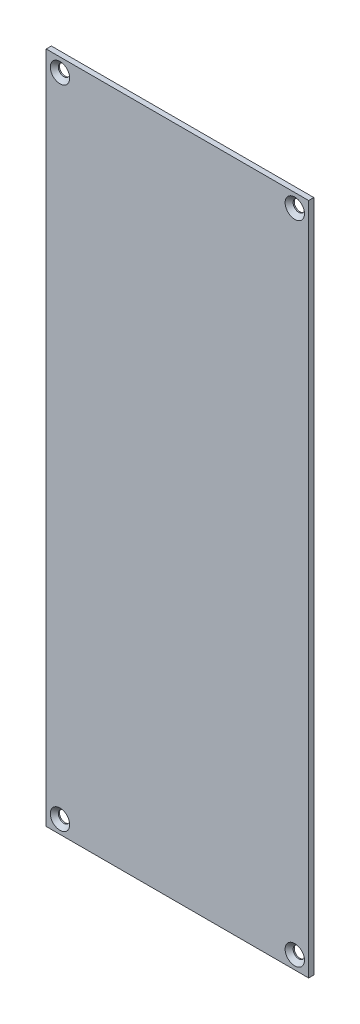
SolidWorks part; units mm, degrees
ref_plane "Front Plane" through (0, 0, 0) normal (0, 0, 1) x (1, 0, 0)
ref_plane "Top Plane" through (0, 0, 0) normal (0, 1, 0) x (1, 0, 0)
ref_plane "Right Plane" through (0, 0, 0) normal (1, 0, 0) x (0, 0, -1)
sketch "Sketch1" plane through (0, 0, 0) normal (0, 0, 1) x (1, 0, 0)
  line L0 (0, 130.33) -> (0, 0)
  line L1 (50.8, 130.33) -> (0, 130.33)
  line L2 (50.8, 0) -> (50.8, 130.33)
  line L3 (0, 0) -> (50.8, 0)
  point P0 (0, 0)
  point P2 (0, 0)
  point P3 (0, 0)
  point P4 (0, 0)
  point P5 (0, 0)
  dimension "D1" = 50.8
  dimension "D2" = 130.33
extrude "Boss-Extrude1" add sketch "Sketch1" along normal blind 1
hole_wizard "CSK for M2 Flat Head Machine Screw1" positions "Sketch6" profile "Sketch4" countersink size "M2" standard "ANSI Metric" end condition up to next
sketch "Sketch6" plane through (0, 0, 1) normal (0, 0, 1) x (1, 0, 0)
  line L2 (2.6725, 127.7025) -> (48.1225, 127.7025) construction
  line L3 (48.1225, 127.7025) -> (48.1225, 2.5625) construction
  line L4 (48.1225, 2.5625) -> (2.6725, 2.5625) construction
  line L5 (2.6725, 2.5625) -> (2.6725, 127.7025) construction
  line L16 (50.8, 130.33) -> (0, 130.33) construction
  line L17 (0, 130.33) -> (0, 0) construction
  point P3 (48.1225, 127.7025)
  point P6 (2.6725, 2.5625)
  point P9 (48.1225, 2.5625)
  point P15 (2.6725, 127.7025)
  point P74 (0.6945, 0.6945)
  point P75 (42.7862, 126.8117)
  point P76 (0, 0)
  dimension "D1" = 2.6275
  dimension "D2" = 2.6725
  dimension "D3" = 45.45
  dimension "D4" = 125.14
sketch "Sketch4" plane through (48.1225, 127.7025, 1) normal (1, 0, 0) x (0, -1, 0)
  line L0 (0, 0) -> (0, 1)
  line L1 (0, 1) -> (1.1, 1)
  line L2 (1.1, 1) -> (1.1, 0.775)
  line L3 (1.1, 0.775) -> (1.875, 0)
  line L5 (1.875, 0) -> (0, 0)
  line L6 (-1.1, 0.775) -> (-1.875, 0) construction
  line L11 (0, -6.35) -> (0, 107.95) construction
  dimension "Thru Hole Dia." = 2.2
  dimension "Thru Hole Depth" = 1
  dimension "Near C'Sink Dia." = 3.75
  dimension "Near C'Sink Angle" = 90
